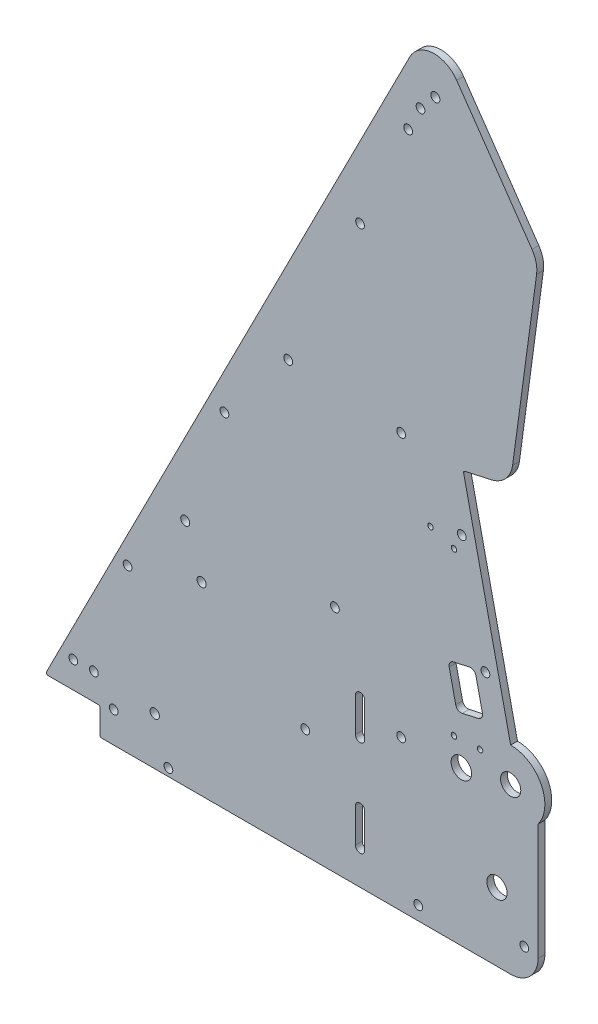
SolidWorks part; units mm, degrees
other "Markup1"
sketch "Sketch5"
ref_plane "Front Plane" through (0, 0, 0) normal (0, 0, 1) x (1, 0, 0)
ref_plane "Top Plane" through (0, 0, 0) normal (0, 1, 0) x (1, 0, 0)
ref_plane "Right Plane" through (0, 0, 0) normal (1, 0, 0) x (0, 0, -1)
sketch "Sketch1" plane through (0, 0, 0) normal (0, 0, 1) x (1, 0, 0)
  line L1 (228.6, -12.7) -> (228.6, 53.975)
  line L2 (178.7547, 351.4131) -> (0, 0)
  line L3 (228.6, 279.4) -> (178.7547, 351.4131)
  line L5 (0, 0) -> (25.4, 0)
  line L6 (25.4, 0) -> (25.4, -12.7)
  line L7 (25.4, -12.7) -> (228.6, -12.7)
  line L9 (215.9, 79.375) -> (193.9097, 178.5667)
  line L10 (193.9097, 178.5667) -> (215.6079, 183.377)
  line L11 (215.6079, 183.377) -> (228.6, 279.4)
  arc A0 (228.6, 53.975) -> (215.9, 79.375) centre (215.9, 63.5) ccw
  dimension "D7" = 12.7
  dimension "D8" = 76.2
  dimension "D10" = 31.75
  dimension "D2" = 292.1
  dimension "D3" = 25.4
  dimension "D4" = 215.9
  dimension "D5" = 394.2644
  dimension "D6" = 203.2
  dimension "D9" = 63.039
  dimension "D11" = 101.6
  dimension "D12" = 12.5
  dimension "D13" = 22.225
extrude "Boss-Extrude1" add sketch "Sketch1" along normal blind 3.175
sketch "Sketch2" plane through (0, 0, 3.175) normal (0, 0, 1) x (1, 0, 0)
  line L0 (178.7547, 351.4131) -> (0, 0) construction
  line L1 (25.4, -12.7) -> (228.6, -12.7) construction
  line L2 (215.9, 79.375) -> (193.9097, 178.5667) construction
  line L3 (193.9097, 178.5667) -> (215.6079, 183.377) construction
  line L4 (215.9, 79.375) -> (193.9097, 178.5667) construction
  line L5 (64.9432, 94.0578) -> (72.5445, 73.1732) construction
  line L6 (64.9432, 94.0578) -> (89.8317, 94.0578) construction
  line L10 (228.6, -12.7) -> (228.6, 53.975) construction
  circle A0 centre (64.9432, 94.0578) radius 2.0955
  circle A1 centre (180.975, 322.1643) radius 2.0955
  circle A2 centre (72.5445, 73.1732) radius 2.0955
  circle A3 centre (193.2078, 152.3944) radius 2.032
  circle A4 centre (215.9, 63.5) radius 4.699
  circle A7 centre (173.0375, -6.35) radius 2.032
  circle A8 centre (204.203, 102.7985) radius 2.032
  circle A26 centre (209.55, 19.05) radius 4.699
  arc A30 (228.6, 53.975) -> (215.9, 79.375) centre (215.9, 63.5) ccw construction
  circle A31 centre (165.1, 179.3875) radius 2.032
  dimension "D3" = 4.191
  dimension "D5" = 4.191
  dimension "D9" = 4.191
  dimension "D20" = 9.398
  dimension "D23" = 9.398
  dimension "D18" = 4.064
  dimension "D26" = 4.064
  dimension "D14" = 4.064
  dimension "D2" = 15.24
  dimension "D6" = 15.24
  dimension "D7" = 22.225
  dimension "D21" = 44.45
  dimension "D22" = 6.35
  dimension "D19" = 160.3375
  dimension "D24" = 44.45
  dimension "D25" = 6.35
  dimension "D27" = 25.4
  dimension "D28" = 50.8
  dimension "D29" = 6.35
  dimension "D17" = 6.35
  dimension "D33" = 55.5625
  dimension "D15" = 114.3
  dimension "D4" = 180.975
  dimension "D8" = 70
extrude "Cut-Extrude1" cut sketch "Sketch2" against normal through all
sketch "Sketch7" plane through (0, 0, 3.175) normal (0, 0, 1) x (1, 0, 0)
  line L0 (146.05, 3.175) -> (146.05, 19.05) construction
  line L1 (143.891, 3.175) -> (143.891, 19.05)
  line L2 (148.209, 3.175) -> (148.209, 19.05)
  line L3 (146.05, 47.625) -> (146.05, 63.5) construction
  line L4 (143.891, 47.625) -> (143.891, 63.5)
  line L5 (148.209, 47.625) -> (148.209, 63.5)
  line L6 (25.4, -12.7) -> (228.6, -12.7) construction
  line L12 (228.6, -12.7) -> (228.6, 53.975) construction
  line L13 (25.4, -12.7) -> (228.6, -12.7) construction
  arc A0 (143.891, 3.175) -> (148.209, 3.175) centre (146.05, 3.175) ccw
  arc A1 (148.209, 19.05) -> (143.891, 19.05) centre (146.05, 19.05) ccw
  arc A2 (143.891, 47.625) -> (148.209, 47.625) centre (146.05, 47.625) ccw
  arc A3 (148.209, 63.5) -> (143.891, 63.5) centre (146.05, 63.5) ccw
  circle A8 centre (50.8, 9.525) radius 2.159
  circle A10 centre (134.3935, 93.98) radius 2.032 construction
  circle A11 centre (134.3935, 93.98) radius 2.032
  point P2 (146.05, 11.1125)
  point P9 (146.05, 55.5625)
  dimension "D1" = 4.318
  dimension "D5" = 4.318
  dimension "D2" = 15.875
  dimension "D3" = 15.875
  dimension "D4" = 44.45
  dimension "D6" = 95.25
  dimension "D7" = 82.55
  dimension "D8" = 15.875
  dimension "D9" = 22.225
extrude "Cut-Extrude2" cut sketch "Sketch7" against normal through all
sketch "Sketch10" plane through (0, 0, 3.175) normal (0, 0, 1) x (1, 0, 0)
  circle A1 centre (165.1, 57.15) radius 2.032
  circle A2 centre (120.65, 38.1) radius 2.032
  circle A3 centre (13.0465, 12.3347) radius 2.032
  circle A4 centre (22.5715, 12.3347) radius 2.032
  circle A5 centre (38.2114, 62.6398) radius 2.032
  dimension "D1" = 4.064
  dimension "D2" = 4.064
  dimension "D4" = 63.5
  dimension "D5" = 69.85
extrude "Cut-Extrude3" cut sketch "Sketch10" against normal up to next
fillet "Fillet1" radius 12.7 4 edges at (228.6, -12.7, 1.5875) (178.7547, 351.4131, 1.5875) (215.6079, 183.377, 1.5875) (228.6, 279.4, 1.5875)
fillet "Fillet2" radius 0.7937 4 edges at (25.4, -12.7, 1.5875) (25.4, 0, 1.5875) (193.9097, 178.5667, 1.5875) (0, 0, 1.5875)
sketch "Sketch12" plane through (0, 0, 3.175) normal (0, 0, 1) x (1, 0, 0)
  circle A0 centre (31.75, 1.5875) radius 2.032
  circle A1 centre (222.25, 1.5875) radius 2.032
  circle A2 centre (57.15, -9.2075) radius 2.032
  circle A3 centre (57.15, -9.2075) radius 2.286 construction
  dimension "D1" = 4.064
  dimension "D2" = 4.064
extrude "Cut-Extrude5" cut sketch "Sketch12" against normal through all
sketch "Sketch13" plane through (0, 0, 3.175) normal (0, 0, 1) x (1, 0, 0)
  line L2 (194.6847, 178.7385) -> (206.9592, 181.4597) construction
  line L5 (199.2434, 101.699) -> (189.6226, 145.0954) construction
  line L6 (189.6022, 69.9806) -> (201.7089, 70.5092) construction
  line L7 (186.8444, 98.9502) -> (199.2434, 101.699)
  line L8 (186.8444, 98.9502) -> (190.9676, 80.3518)
  line L9 (190.9676, 80.3518) -> (203.3665, 83.1006)
  line L10 (199.2434, 101.699) -> (203.3665, 83.1006)
  line L11 (189.6022, 69.9806) -> (190.9676, 80.3518) construction
  line L12 (201.7089, 70.5092) -> (203.3665, 83.1006) construction
  line L13 (215.9, 79.375) -> (194.0815, 177.7917) construction
  line L14 (178.7216, 148.5324) -> (189.6226, 145.0954) construction
  circle A0 centre (189.6022, 69.9806) radius 1.27
  circle A1 centre (201.7089, 70.5092) radius 1.27
  circle A2 centre (178.7216, 148.5324) radius 1.27
  circle A3 centre (189.6226, 145.0954) radius 1.27
  dimension "D7" = 2.54
  dimension "D2" = 11.43
  dimension "D3" = 76.2
  dimension "D4" = 12.7
  dimension "D5" = 19.05
  dimension "D6" = 120
  dimension "D8" = 110
  dimension "D9" = 80
  dimension "D10" = 12.7
  dimension "D11" = 44.45
  dimension "D12" = 11.43
extrude "Cut-Extrude6" cut sketch "Sketch13" against normal through all both and the other way through all
sketch "Sketch14" plane through (0, 0, 3.175) normal (0, 0, 1) x (1, 0, 0)
  line L0 (26.1937, -12.7) -> (215.9, -12.7) construction
  line L1 (228.6, 0) -> (228.6, 53.975) construction
  circle A0 centre (146.05, 254) radius 2.032
  circle A1 centre (112.7125, 182.5625) radius 2.032
  dimension "D1" = 4.064
  dimension "D2" = 195.2625
  dimension "D3" = 115.8875
  dimension "D4" = 82.55
  dimension "D5" = 266.7
extrude "Cut-Extrude7" cut sketch "Sketch14" against normal up to next
sketch "Sketch15" plane through (0, 0, 3.175) normal (0, 0, 1) x (1, 0, 0)
  line L0 (169.1053, 332.4434) -> (0.5868, 1.1536) construction
  circle A0 centre (83.1368, 146.6315) radius 2.032
  circle A1 centre (174.0995, 314.25) radius 2.032
  circle A2 centre (168.3414, 302.9303) radius 2.032
  circle A3 centre (174.0995, 314.25) radius 1.905 construction
  circle A4 centre (168.3414, 302.9303) radius 1.905 construction
  dimension "D1" = 4.064
  dimension "D4" = 4.064
  dimension "D2" = 7.62
  dimension "D3" = 82.55
extrude "Cut-Extrude8" cut sketch "Sketch15" against normal through all
fillet "Fillet3" radius 2.54 4 edges at (199.2434, 101.699, 1.5875) (186.8444, 98.9502, 1.5875) (190.9676, 80.3518, 1.5875) (203.3665, 83.1006, 1.5875)
sketch "Sketch16" plane through (0, 0, 3.175) normal (0, 0, 1) x (1, 0, 0)
  line L0 (228.6, 0) -> (228.6, 53.975) construction
  line L1 (26.1937, -12.7) -> (215.9, -12.7) construction
  circle A0 centre (193.04, 58.801) radius 4.7625
  point P2 (194.084, 58.8033)
  dimension "D1" = 9.525
  dimension "D2" = 35.56
  dimension "D3" = 71.501
extrude "Cut-Extrude9" cut sketch "Sketch16" against normal through all
equation "\"D6@Sketch2\"=\"D2@Sketch2\""
